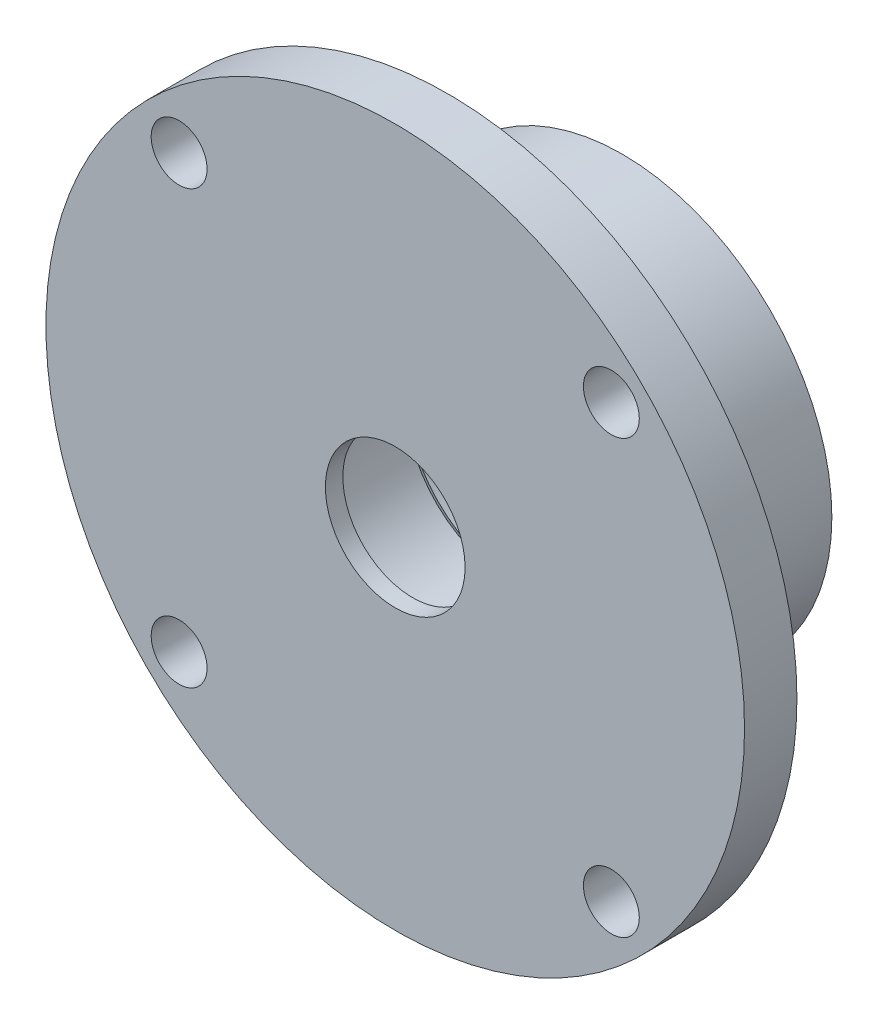
SolidWorks part; units mm, degrees
material "Литая углеродистая сталь"
ref_plane "Спереди" through (0, 0, 0) normal (0, 0, 1) x (1, 0, 0)
ref_plane "Сверху" through (0, 0, 0) normal (0, 1, 0) x (1, 0, 0)
ref_plane "Справа" through (0, 0, 0) normal (1, 0, 0) x (0, 0, -1)
sketch "Эскиз1" plane through (0, 0, 0) normal (0, 1, 0) x (1, 0, 0)
  line L0 (-4, 0) -> (-20, 0)
  line L1 (-20, 0) -> (-20, 3)
  line L2 (-20, 3) -> (-12, 3)
  line L3 (-12, 3) -> (-12, 13)
  line L4 (-12, 13) -> (-9.5, 13)
  line L5 (-9.5, 13) -> (-9.5, 7)
  line L8 (-9.5, 7) -> (-6, 7)
  line L9 (-6, 7) -> (-6, 1)
  line L10 (-6, 1) -> (-4, 1)
  line L11 (-4, 1) -> (-4, 0)
  line L12 (0, 0) -> (0, 50000) construction
  dimension "D1" = 4
  dimension "D2" = 20
  dimension "D3" = 12
  dimension "D4" = 13
  dimension "D5" = 9.5
  dimension "D6" = 1
  dimension "D7" = 7
  dimension "D8" = 6
  dimension "D9" = 3
revolve "Повернуть1" add sketch "Эскиз1" angle 360 about L12
chamfer "Фаска1" distance 0.4 angle 45 1 edges at (6, 0, -7)
sketch "Эскиз2" plane through (0, 0, 0) normal (0, 0, 1) x (1, 0, 0)
  line L0 (0, 0) -> (20, 0) construction
  circle A0 centre (12.3744, 12.3744) radius 1.6
  circle A1 centre (0, 0) radius 20 construction
  dimension "D2" = 3.2
  dimension "D1" = 45
  dimension "D3" = 17.5
extrude "Вырез-Вытянуть1" cut sketch "Эскиз2" against normal up to next
pattern_circular "Круговой массив1" count 4 over 360 about axis through (0, 0, 0) along (0, 0, 1) of "Вырез-Вытянуть1"
